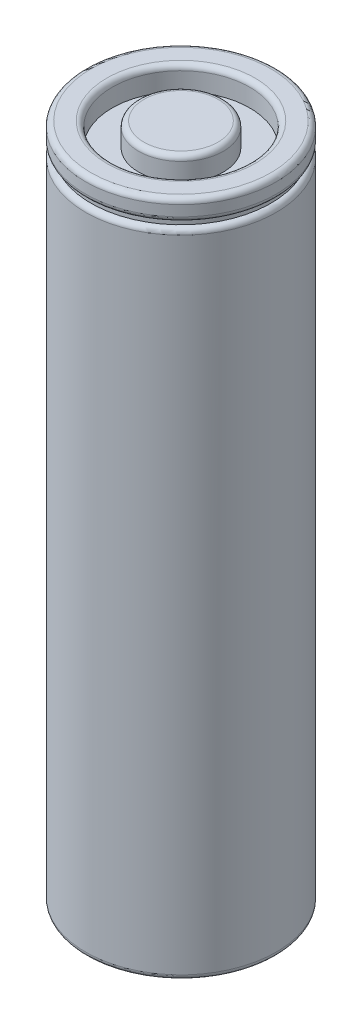
SolidWorks part; units mm, degrees
material "AISI 304"
ref_plane "Front Plane" through (0, 0, 0) normal (0, 0, 1) x (1, 0, 0)
ref_plane "Top Plane" through (0, 0, 0) normal (0, 1, 0) x (1, 0, 0)
ref_plane "Right Plane" through (0, 0, 0) normal (1, 0, 0) x (0, 0, -1)
sketch "Sketch2" plane through (0, 0, 0) normal (1, 0, 0) x (0, 0, -1)
  line L0 (9, 62) -> (8.5, 62)
  line L1 (0, 0) -> (9, 0)
  line L2 (0, 0) -> (0, 64)
  line L3 (0, 64) -> (9, 64)
  line L4 (9, 0) -> (9, 61.5)
  line L5 (8.5, 62) -> (8.5, 61.5)
  line L6 (8.5, 61.5) -> (9, 61.5)
  line L7 (9, 62) -> (9, 64)
  dimension "D1" = 2
  dimension "D2" = 0.5
  dimension "D3" = 0.5
  dimension "D4" = 9
  dimension "D5" = 64
revolve "Revolve1" add sketch "Sketch2" angle 360 about L2
fillet "Fillet1" radius 0.5 3 edges at (0, 0, -9) (0, 61.5, -9) (0, 62, -9)
sketch "Sketch4" plane through (0, 64, 0) normal (0, 1, 0) x (1, 0, 0)
  circle A0 centre (0, 0) radius 6.5
extrude "Cut-Extrude1" cut sketch "Sketch4" against normal blind 2.2
sketch "Sketch5" plane through (0, 61.8, 0) normal (0, 1, 0) x (1, 0, 0)
  circle A0 centre (0, 0) radius 4
  dimension "D1" = 8
extrude "Boss-Extrude1" add sketch "Sketch5" along normal up to surface (2.2 mm away) up to face at (0, 64, 6.5)
fillet "Fillet2" radius 0.5 3 edges at (0, 64, -9) (0, 64, 6.5) (0, 64, 4)
